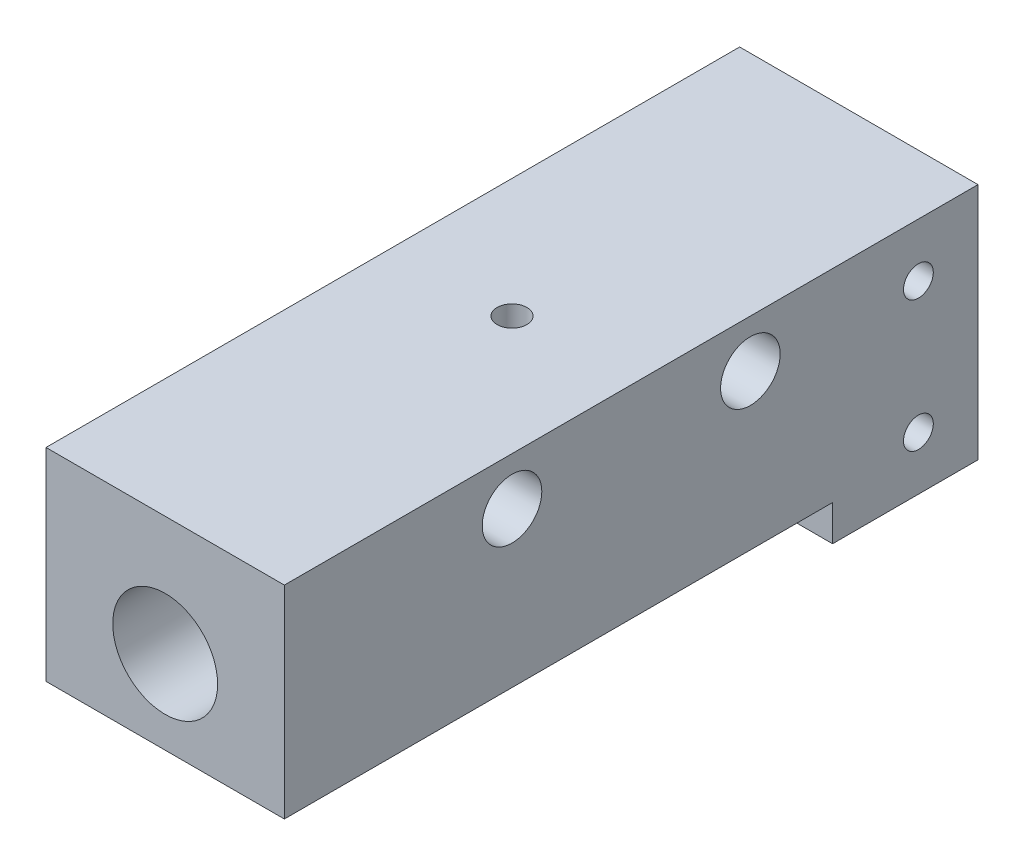
SolidWorks part; units mm, degrees
material "6063-T5"
ref_plane "Piano frontale" through (0, 0, 0) normal (0, 0, 1) x (1, 0, 0)
ref_plane "Piano superiore" through (0, 0, 0) normal (0, 1, 0) x (1, 0, 0)
ref_plane "Piano destro" through (0, 0, 0) normal (1, 0, 0) x (0, 0, -1)
sketch "Schizzo1" plane through (0, 0, 0) normal (0, 0, 1) x (1, 0, 0)
  line L1 (10, -10) -> (-10, -10)
  line L2 (10, -10) -> (10, 10)
  line L3 (10, 10) -> (-10, 10)
  line L4 (-10, -10) -> (-10, 10)
  line L5 (10, -10) -> (-10, 10) construction
  line L6 (10, 10) -> (-10, -10) construction
  point P0 (0, 0)
  dimension "D1" = 20
  dimension "D2" = 20
extrude "Estrusione-Estrusione1" add sketch "Schizzo1" against normal blind 58.2
sketch "Schizzo2" plane through (0, 0, -58.2) normal (0, 0, -1) x (-1, 0, 0)
  circle A0 centre (0, 0) radius 3
  dimension "D1" = 6
extrude "Taglio-Estrusione1" cut sketch "Schizzo2" against normal through all
sketch "Schizzo3" plane through (0, 0, -58.2) normal (0, 0, -1) x (-1, 0, 0)
  point P0 (0, 0)
sketch "Schizzo4" plane through (10, 0, 0) normal (1, 0, 0) x (0, 0, -1)
  line L0 (0, 6) -> (58.2, 6) construction
  line L1 (0, -10) -> (0, 10) construction
  line L2 (58.2, -10) -> (58.2, 10) construction
  line L3 (58.2, 10) -> (0, 10) construction
  line L4 (29.1, 10) -> (29.1, -10) construction
  line L5 (58.2, -10) -> (0, -10) construction
  point P12 (39.1, 6)
  point P17 (19.1, 6)
  dimension "D2" = 20
  dimension "D1" = 4
hole_wizard "Foro filettato G1/8-1" positions "Schizzo8" profile "Schizzo7" tap size "G1/8" standard "BSI"
sketch "Schizzo8" plane through (0, 0, 0) normal (0, 0, 1) x (1, 0, 0)
  point P0 (0, 0)
sketch "Schizzo7" plane through (0, 0, 0) normal (1, 0, 0) x (0, -1, 0)
  line L0 (0, 0) -> (0, 12.6438)
  line L1 (0, 12.6438) -> (4.4, 10)
  line L2 (4.4, 10) -> (4.4, 0)
  line L5 (4.4, 0) -> (0, 0)
  line L10 (0, 12.6438) -> (-4.4, 10) construction
  line L11 (0, -6.35) -> (0, 107.95) construction
  dimension "Tap Drill Dia." = 8.8
  dimension "Tap Drill Depth" = 10
  dimension "Drill Angle" = 118
sketch "Schizzo10" plane through (10, 0, 0) normal (1, 0, 0) x (0, 0, -1)
  line L0 (0, -7) -> (46, -7)
  line L1 (0, -10) -> (0, 10) construction
  line L2 (46, -7) -> (46, -10)
  line L3 (58.2, -10) -> (0, -10) construction
  dimension "D1" = 46
  dimension "D2" = 3
extrude "Taglio-Estrusione5" cut sketch "Schizzo10" against normal through all and the other way through all flip side to cut
sketch "Schizzo11" plane through (0, 10, 0) normal (0, 1, 0) x (1, 0, 0)
  line L0 (0, 58.2) -> (0, 0) construction
  line L1 (10, 58.2) -> (-10, 58.2) construction
  line L2 (10, 29.1) -> (-10, 29.1) construction
  line L3 (10, 58.2) -> (10, 0) construction
  point P10 (0, 29.1)
  point P11 (0, 29.1)
  point P12 (0, 29.1)
hole_wizard "Foro filettato M3-1" positions "Schizzo3D1" profile "Schizzo12" tap size "M3" standard "DIN"
sketch3d "Schizzo3D1"
  point P0 (0, 10, -29.1)
sketch "Schizzo12" plane through (0, 10, -29.1) normal (1, 0, 0) x (0, 0, 1)
  line L0 (0, 0) -> (0, 5.7511)
  line L1 (0, 5.7511) -> (1.25, 5)
  line L2 (1.25, 5) -> (1.25, 0)
  line L5 (1.25, 0) -> (0, 0)
  line L10 (0, 5.7511) -> (-1.25, 5) construction
  line L11 (0, -6.35) -> (0, 107.95) construction
  dimension "Tap Drill Dia." = 2.5
  dimension "Tap Drill Depth" = 5
  dimension "Drill Angle" = 118
hole_wizard "Foro Ø16.0 (16)-1" positions "Schizzo3D3" profile "Schizzo14" hole size "Ø16.0" standard "ISO"
sketch3d "Schizzo3D3"
  point P0 (0, 0, 0)
  point P3 (0, 0, -58.2)
sketch "Schizzo14" plane through (0, 0, -58.2) normal (1, 0, 0) x (0, 1, 0)
  line L0 (0, 0) -> (0, 16.8069)
  line L1 (0, 16.8069) -> (8, 12)
  line L2 (8, 12) -> (8, 0)
  line L5 (8, 0) -> (0, 0)
  line L10 (0, 16.8069) -> (-8, 12) construction
  line L11 (0, -6.35) -> (0, 107.95) construction
  dimension "Hole Dia." = 16
  dimension "Hole Depth" = 12
  dimension "Drill Angle" = 118
sketch "Schizzo15" plane through (10, 0, 0) normal (1, 0, 0) x (0, 0, -1)
  line L0 (46.2, 0) -> (58.2, 0) construction
  line L1 (46.2, 8) -> (46.2, -8) construction
  line L4 (58.2, -10) -> (58.2, 10) construction
  line L6 (58.2, -10) -> (46, -10) construction
  point P5 (53.2, -5.5)
  point P8 (53.2, 5.5)
  dimension "D1" = 5.5
  dimension "D2" = 7
  dimension "D3" = 5
  dimension "D4" = 4.5
hole_wizard "Foro filettato M3-2" positions "Schizzo3D4" profile "Schizzo16" tap size "M3" standard "ISO" end condition through all
sketch3d "Schizzo3D4"
  point P0 (10, 5.5, -53.2)
  point P3 (10, -5.5, -53.2)
sketch "Schizzo16" plane through (10, 5.5, -53.2) normal (0, 1, 0) x (0, 0, -1)
  line L0 (0, 0) -> (0, 20)
  line L1 (0, 20) -> (1.25, 20)
  line L2 (1.25, 20) -> (1.25, 0)
  line L5 (1.25, 0) -> (0, 0)
  line L11 (0, -6.35) -> (0, 107.95) construction
  dimension "Thread Major Dia." = 2.5
  dimension "Thru Tap Drill Depth" = 20
hole_wizard "M4 Clearance Hole1" positions "3DSketch5" profile "Sketch4" hole size "M4" standard "ISO" end condition through all
sketch3d "3DSketch5"
  point P0 (10, 6, -19.1)
  point P4 (10, 6, -39.1)
sketch "Sketch4" plane through (10, 6, -19.1) normal (0, 1, 0) x (0, 0, -1)
  line L0 (0, 0) -> (0, 20)
  line L1 (0, 20) -> (2.5, 20)
  line L2 (2.5, 20) -> (2.5, 0)
  line L5 (2.5, 0) -> (0, 0)
  line L11 (0, -6.35) -> (0, 107.95) construction
  dimension "Thru Hole Dia." = 5
  dimension "Thru Hole Depth" = 20
